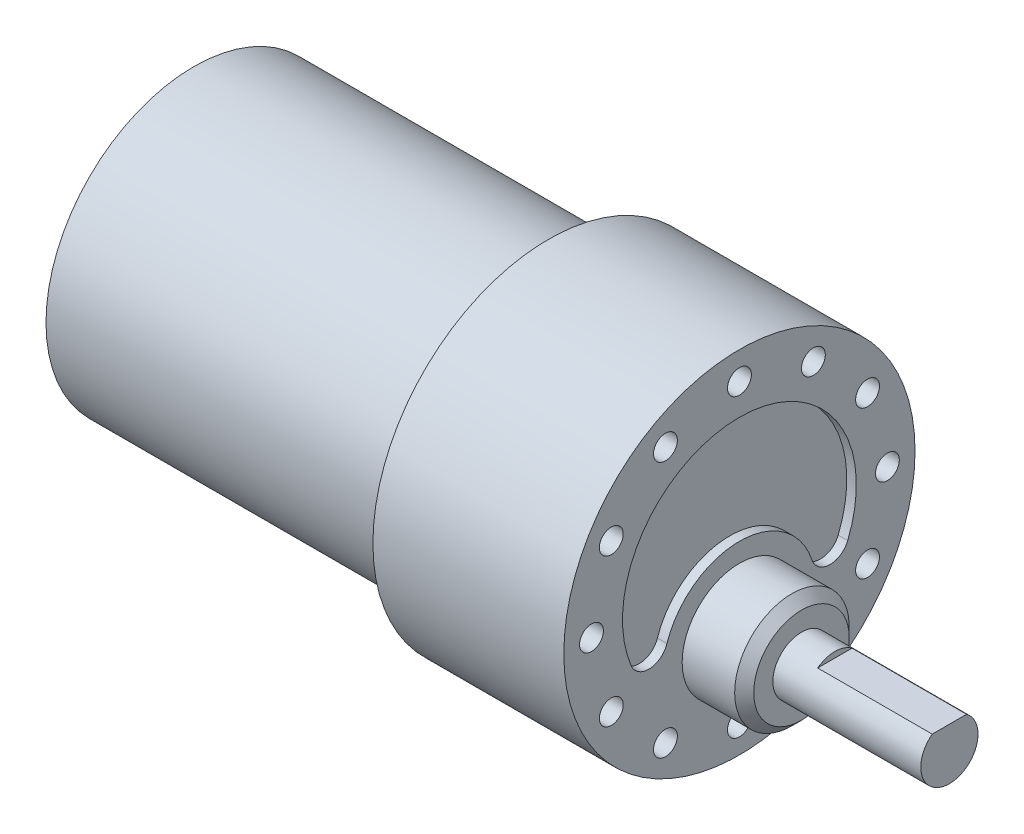
SolidWorks part; units mm, degrees
material "Plain Carbon Steel"
ref_plane "Front Plane" through (0, 0, 0) normal (0, 0, 1) x (1, 0, 0)
ref_plane "Top Plane" through (0, 0, 0) normal (0, 1, 0) x (1, 0, 0)
ref_plane "Right Plane" through (0, 0, 0) normal (1, 0, 0) x (0, 0, -1)
sketch "Sketch1" plane through (0, 0, 0) normal (1, 0, 0) x (0, 0, -1)
  line L0 (0, 0) -> (0, -7) construction
  line L1 (-18.4, 0) -> (-36.0858, 0) construction
  line L2 (0, 0) -> (-15.5, 0) construction
  line L3 (0, 0) -> (-7.75, 13.4234) construction
  line L4 (0, 0) -> (0, 15.5) construction
  line L5 (0, 0) -> (7.75, 13.4234) construction
  line L6 (0, 0) -> (15.5, 0) construction
  line L7 (0, 0) -> (7.75, -13.4234) construction
  line L8 (0, 0) -> (0, -15.5) construction
  line L9 (0, 0) -> (-7.75, -13.4234) construction
  line L10 (0, 0) -> (-13.4234, -7.75) construction
  line L11 (0, 0) -> (13.4234, -7.75) construction
  line L12 (0, 0) -> (13.4234, 7.75) construction
  line L13 (0, 0) -> (-13.4234, 7.75) construction
  circle A0 centre (0, 0) radius 18.4
  circle A1 centre (0, -7) radius 6
  circle A2 centre (0, -7) radius 3
  circle A3 centre (0, 0) radius 15.5
  point P7 (0, 15.5)
  point P8 (0, -15.5)
  point P9 (-15.5, 0)
  point P10 (15.5, 0)
  point P11 (-7.75, 13.4234)
  point P12 (7.75, 13.4234)
  point P15 (7.75, -13.4234)
  point P16 (-7.75, -13.4234)
  dimension "D1" = 36.8
  dimension "D3" = 12
  dimension "D4" = 6
  dimension "D5" = 31
  dimension "D2" = 7
  dimension "D6" = 15.5
  dimension "D7" = 120
extrude "Boss-Extrude1" add sketch "Sketch1" along normal blind 6.5 contours A1 A2 region at (0, -7, 5.8303)
extrude "Boss-Extrude2" add sketch "Sketch1<3>" along normal blind 22 contours A2 region at (0, -7, 0)
sketch "Sketch1<3>" plane through (0, 0, 0) normal (1, 0, 0) x (0, 0, -1) same geometry as "Sketch1"
extrude "Boss-Extrude3" add sketch "Sketch1<4>" against normal blind 20 separate body contours A0 A3 | A3 A1 | A1 A2 | A2 region at (0, 0, 17.8796) region at (0, -7, 5.8303) region at (0, -7, 0) region at (0, 1.2338, 0)
sketch "Sketch1<4>" plane through (0, 0, 0) normal (1, 0, 0) x (0, 0, -1) same geometry as "Sketch1"
extrude "Boss-Extrude4" add sketch "Sketch1<5>" against normal blind 57.15 contours A3 A1 | A2 | A1 A2 region at (0, -7, 5.8303) region at (0, -7, 0) region at (0, 1.2338, 0)
sketch "Sketch1<5>" plane through (0, 0, 0) normal (1, 0, 0) x (0, 0, -1) same geometry as "Sketch1"
hole_wizard "M3x0.5 Tapped Hole1" positions "Sketch3" profile "Sketch2" tap size "M3x0.5" standard "ANSI Metric"
sketch "Sketch3" plane through (0, 0, 0) normal (1, 0, 0) x (0, 0, -1)
  point P0 (-13.4234, 7.75)
  point P3 (-15.5, 0)
  point P6 (-13.4234, -7.75)
  point P9 (-7.75, -13.4234)
  point P12 (0, -15.5)
  point P15 (7.75, -13.4234)
  point P18 (13.4234, -7.75)
  point P21 (15.5, 0)
  point P24 (13.4234, 7.75)
  point P27 (7.75, 13.4234)
  point P30 (0, 15.5)
  point P33 (-7.75, 13.4234)
sketch "Sketch2" plane through (0, 7.75, 13.4234) normal (0, 1, 0) x (0, 0, -1)
  line L0 (0, 0) -> (0, 5.4261)
  line L1 (0, 5.4261) -> (1.25, 4.675)
  line L2 (1.25, 4.675) -> (1.25, 0)
  line L5 (1.25, 0) -> (0, 0)
  line L10 (0, 5.4261) -> (-1.25, 4.675) construction
  line L11 (0, -6.35) -> (0, 107.95) construction
  dimension "Tap Drill Dia." = 2.5
  dimension "Tap Drill Depth" = 4.675
  dimension "Drill Angle" = 118
cosmetic thread "Hole Thread1" parameters "D1"=3.175, "D2"=3
cosmetic thread "Hole Thread2" parameters "D1"=3.175, "D2"=3
cosmetic thread "Hole Thread3" parameters "D1"=3.175, "D2"=3
cosmetic thread "Hole Thread4" parameters "D1"=3.175, "D2"=3
cosmetic thread "Hole Thread5" parameters "D1"=3.175, "D2"=3
cosmetic thread "Hole Thread6" parameters "D1"=3.175, "D2"=3
cosmetic thread "Hole Thread7" parameters "D1"=3.175, "D2"=3
cosmetic thread "Hole Thread8" parameters "D1"=3.175, "D2"=3
cosmetic thread "Hole Thread9" parameters "D1"=3.175, "D2"=3
cosmetic thread "Hole Thread10" parameters "D1"=3.175, "D2"=3
cosmetic thread "Hole Thread11" parameters "D1"=3.175, "D2"=3
cosmetic thread "Hole Thread12" parameters "D1"=3.175, "D2"=3
sketch "Sketch4" plane through (0, 0, 0) normal (1, 0, 0) x (0, 0, -1)
  arc A1 (11.3474, -4.6151) -> (-11.3474, -4.6151) centre (0, 0) ccw
  circle A2 centre (0, -7) radius 8
  arc A3 (7.5958, -4.4893) -> (-7.5958, -4.4893) centre (0, -7) ccw
  circle A4 centre (-7.75, 13.4234) radius 1.25 construction
  arc A5 (-7.5958, -4.4893) -> (-11.3474, -4.6151) centre (-9.4948, -3.8616) cw
  arc A6 (7.5958, -4.4893) -> (11.3474, -4.6151) centre (9.4948, -3.8616) ccw
  dimension "D2" = 2
  dimension "D3" = 2
  dimension "D4" = 2
  dimension "D1" = 2
extrude "Cut-Extrude1" cut sketch "Sketch4" against normal blind 1
sketch "Sketch5" plane through (22, 0, 0) normal (1, 0, 0) x (0, 0, -1)
  line L0 (-1.8, -4.6) -> (1.8, -4.6)
  circle A1 centre (0, -7) radius 3
  arc A2 (1.8, -4.6) -> (-1.8, -4.6) centre (0, -7) ccw
  dimension "D2" = 5.4
  dimension "D1" = 0
extrude "Cut-Extrude2" cut sketch "Sketch5" against normal blind 12
chamfer "Chamfer1" distance 1 angle 45 1 edges at (6.5, -7, -6)
